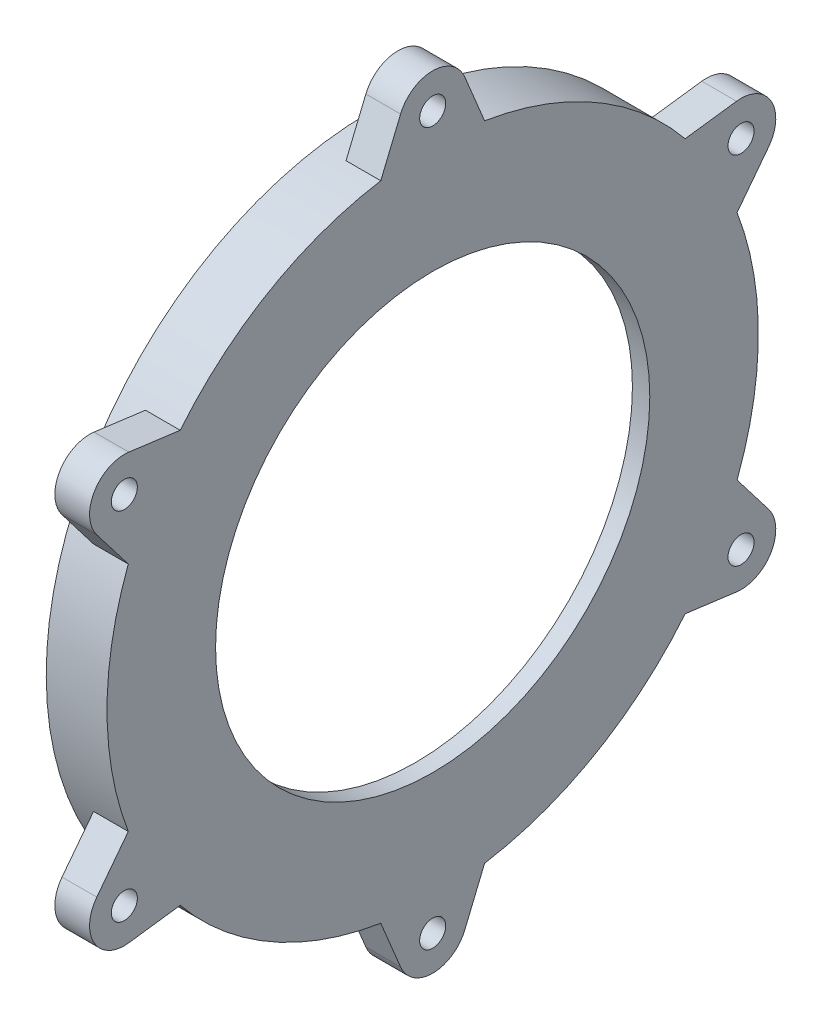
SolidWorks part; units mm, degrees
note: The reader was unsure of these and kept them because the rebuilt part matched: shared geometry of "TooCutSke<2>".
ref_plane "Plane1" through (0, 0, 0) normal (0, 0, 1) x (1, 0, 0)
ref_plane "Plane2" through (0, 0, 0) normal (0, 1, 0) x (1, 0, 0)
ref_plane "Plane3" through (0, 0, 0) normal (1, 0, 0) x (0, 0, -1)
sketch "HoldingSke" plane through (0, 0, 0) normal (0, 1, 0) x (1, 0, 0)
  line L0 (0, 0) -> (0.3746, -0.9272)
  line L1 (-15, 0) -> (100, 0) construction
  line L2 (0, 0) -> (-2.1039, 2.3779)
  line L3 (0, 0) -> (-11.863, 4.5341)
  line L4 (0, 0) -> (3.2351, 8.0072)
  line L5 (0, 0) -> (-23.7986, -8.8762)
  line L6 (0, 0) -> (-10.5278, -7.1032)
  line L7 (-2.1039, 2.3779) -> (3.3635, 27.1825)
  line L8 (-76.2, 3.3779) -> (-54.61, 3.3779)
  line L9 (-71.009, 38.7566) -> (-53.1078, 45.2721)
  line L10 (-76.2, 71.12) -> (104.1128, 71.12)
  line L11 (0, 0) -> (-5, 0)
  line L12 (-76.2, 101.6) -> (-76.162, 101.6)
  line L13 (24.9733, 27.94) -> (52.9518, 28.4284)
  line L14 (24.9733, 27.94) -> (24.9743, 27.94)
  line L15 (24.9733, 27.94) -> (100.4006, 29.5858)
  circle A0 centre (0, 0) radius 13
  circle A1 centre (0, 0) radius 12.7
  circle A2 centre (0, 0) radius 12.7
  dimension "MHD" = 25.4
  dimension "Hub_dia" = 25.4
  dimension "Diameter" = 26
  dimension "Num_teeth" = 68
  dimension "Pitch" = 1
  dimension "Overall_len" = 25.4
  dimension "Show_teeth" = 68
  dimension "Thickness" = 12.7
  dimension "OAL" = 25.4001
  dimension "T_dim" = 21.59
  dimension "Ap" = 20
  dimension "H" = 19.05
  dimension "Pitch_radius" = 180.3128
  dimension "Width" = 5
  dimension "Backlash" = 0.038
  dimension "Addendum_fac" = 1
  dimension "Dedendum_fac" = 1.25
  dimension "Clearance_fac" = 0.25
  dimension "Dedendum_add" = 0.001
  dimension "Module" = 1
sketch "BasProSke" plane through (0, 0, 0) normal (0, 1, 0) x (1, 0, 0)
  line L0 (-10, 0) -> (60, 0) construction
  line L1 (0, 33) -> (0, 35.2764)
  line L2 (0, 33) -> (5, 33)
  line L3 (5, 33) -> (5, 35.2764)
  line L4 (5, 35.2764) -> (0, 35.2764)
  dimension "Thickness" = 5
  dimension "Diameter" = 70.5528
  dimension "Inside_diameter" = 66
revolve "Base-Revolve" add sketch "BasProSke" angle 360 about L0
sketch "Эскиз1" plane through (0, 0, 0) normal (1, 0, 0) x (0, 0, -1)
  circle A0 centre (0, 0) radius 35.2764
  circle A1 centre (0, 0) radius 37.5
  circle A2 centre (0, 0) radius 35.2764 construction
  dimension "D1" = 75
extrude "Бобышка-Вытянуть1" add sketch "Эскиз1" along normal blind 5
sketch "Эскиз2" plane through (0, 0, 0) normal (1, 0, 0) x (0, 0, -1)
  circle A0 centre (0, 0) radius 33
curve "Спираль1" pitch 797.27 height 10 radius 33 left hand yes centre (0, 0, 0) axis (1, 0, 0) start towards (0, 0, 1)
sketch "TooCutSke" plane through (0, 0, 0) normal (1, 0, 0) x (0, 0, -1)
  line L3 (0.8803, 33.9886) -> (0.8803, 53.6633) construction
  line L4 (0, 0) -> (0, 59.563) construction
  line L5 (0, 0) -> (-3.1556, 68.2546) construction
  line L6 (-15.0631, 28.0889) -> (36.4744, 30.4716) construction
  circle A0 centre (0, 0) radius 34 construction
  circle A1 centre (0, 0) radius 35.251 construction
  circle A2 centre (0, 0) radius 28.7546 construction
  circle A3 centre (0, 0) radius 32.9746 construction
  arc A4 (1.2265, 32.9518) -> (0.3554, 35.2492) centre (-15.0631, 28.0889) ccw
  arc A5 (1.2265, 32.9518) -> (-1.2265, 32.9518) centre (0, 0) ccw
  arc A6 (0.3554, 35.2492) -> (-0.3554, 35.2492) centre (0, 0) ccw
  arc A7 (-0.3554, 35.2492) -> (-1.2265, 32.9518) centre (15.0631, 28.0889) ccw
  dimension "Pitch_dia" = 68
  dimension "Base_dia" = 57.5092
  dimension "Root_dia" = 70.502
  dimension "Overcut_dia" = 65.9492
  dimension "Flank_rad" = 17
  dimension "Half_ang" = 2.647
  dimension "Half_CT" = 0.8803
extrude "ToothCut" [suppressed] cut sketch "TooCutSke" along normal through all
sweep "Вырез-По траектории1" cut profiles "TooCutSke<2>" path "Спираль1" align with end faces yes
sketch "TooCutSke<2>" plane through (0, 0, 0) normal (1, 0, 0) x (0, 0, -1) same geometry as "TooCutSke"
fillet "Breaks" [suppressed] radius 0.1
fillet "RootFillets" [suppressed] radius 0.251
pattern_circular "TeethCuts" count 68 every 5.294 about axis through (-10, 0, 0) along (1, 0, 0) of "Вырез-По траектории1"
sketch "Эскиз3" plane through (5, 0, 0) normal (1, 0, 0) x (0, 0, -1)
  circle A0 centre (0, 0) radius 37.5
  circle A1 centre (0, 0) radius 37.5 construction
  circle A2 centre (0, 0) radius 25
  dimension "D1" = 50
extrude "Бобышка-Вытянуть2" add sketch "Эскиз3" along normal blind 2
sketch "Эскиз4" plane through (7, 0, 0) normal (1, 0, 0) x (0, 0, -1)
  line L0 (-3.6955, 42.5307) -> (-5.978, 37.0205)
  line L1 (0, 41) -> (0, 37.5) construction
  line L2 (3.6955, 42.5307) -> (5.978, 37.0205)
  circle A0 centre (0, 41) radius 1.5
  arc A1 (3.6955, 42.5307) -> (-3.6955, 42.5307) centre (0, 41) ccw
  circle A2 centre (0, 0) radius 37.5 construction
  arc A3 (-5.978, 37.0205) -> (5.978, 37.0205) centre (0, 0) cw
  dimension "D1" = 3
  dimension "D2" = 8
  dimension "D3" = 45
  dimension "D4" = 41
extrude "Бобышка-Вытянуть3" add sketch "Эскиз4" against normal blind 4
pattern_circular "Круговой массив1" count 6 over 360 about axis through (0, 0, 0) along (1, 0, 0) of "Бобышка-Вытянуть3"
equation "' \"Module@HoldingSke\" = 6.35"
equation "' \"Num_teeth@HoldingSke\" = 24"
equation "' \"Ap@HoldingSke\" =  14.5"
equation "' \"Ap@HoldingSke\" = 14.5"
equation "' \"Width@HoldingSke\" = 12"
equation "' \"Diameter@HoldingSke\" = 8 * 25.4"
equation "' \"Show_teeth@HoldingSke\" = 100"
equation "' \"Backlash@HoldingSke\" = 0.009 * 25.4"
equation "' \"Addendum_fac@HoldingSke\" = 1.0"
equation "' \"Dedendum_fac@HoldingSke\" = 1.25"
equation "' \"Dedendum_add@HoldingSke\" = 0.00005 * 25.4"
equation "' \"Clearance_fac@HoldingSke\" = 0.25"
equation "\"Pitch@HoldingSke\" = 1 / \"Module@HoldingSke\" "
equation "\"Overcut_dia@TooCutSke\" = (\"Num_teeth@HoldingSke\" - 2 * \"Addendum_fac@HoldingSke\") / \"Pitch@HoldingSke\" - 0.002 * 25.4"
equation "\"Pitch_dia@TooCutSke\" = \"Num_teeth@HoldingSke\" / \"Pitch@HoldingSke\""
equation "\"Base_dia@TooCutSke\" = \"Num_teeth@HoldingSke\" / \"Pitch@HoldingSke\" * cos((\"Ap@HoldingSke\"  * 3.14159265 / 180)) * 0.90"
equation "\"Root_dia@TooCutSke\" = \"Num_teeth@HoldingSke\"  / \"Pitch@HoldingSke\" + 2 *  \"Dedendum_fac@HoldingSke\"/ \"Pitch@HoldingSke\" + \"Dedendum_add@HoldingSke\" * 2"
equation "\"Half_ang@TooCutSke\" = 180 / \"Num_teeth@HoldingSke\""
equation "\"Half_CT@TooCutSke\" = \"Num_teeth@HoldingSke\" / \"Pitch@HoldingSke\" * sin((3.14159265 / 2 / \"Num_teeth@HoldingSke\")) / 2 + 10 * \"Backlash@HoldingSke\" / 4"
equation "\"Flank_rad@TooCutSke\" = \"Num_teeth@HoldingSke\" / \"Pitch@HoldingSke\" / 4"
equation "\"Radius@RootFillets\"= \"Clearance_fac@HoldingSke\" / \"Pitch@HoldingSke\" + \"Dedendum_add@HoldingSke\""
equation "\"Break_rad@Breaks\" = 0.02 / \"Pitch@HoldingSke\" * 5"
equation "\"Num_teeth@TeethCuts\" = int( \"Show_teeth@HoldingSke\" ) + 1"
equation "\"Num_teeth@TeethCuts\" = ((sgn( \"Num_teeth@TeethCuts\" - \"Num_teeth@HoldingSke\" )-1)*( \"Num_teeth@TeethCuts\" - \"Num_teeth@HoldingSke\" ))/-2+ \"Num_teeth@HoldingSke\""
equation "\"Num_teeth@TeethCuts\" = ((sgn( \"Num_teeth@TeethCuts\" - 2.0)+1)*( \"Num_teeth@TeethCuts\" - 2.0))/2 +2.0"
equation "\"Angle@TeethCuts\" = 360.0 / \"Num_teeth@HoldingSke\""
equation "\"Diameter@BasProSke\" = \"Num_teeth@HoldingSke\"  / \"Pitch@HoldingSke\" + 2 *  \"Dedendum_fac@HoldingSke\"/ \"Pitch@HoldingSke\" + \"Dedendum_add@HoldingSke\" * 2 + 0.002 * 25.4"
equation "\"Diameter@BasProSke\" = ((sgn( \"Diameter@BasProSke\"  - \"Diameter@HoldingSke\" )+1)*( \"Diameter@BasProSke\"  - \"Diameter@HoldingSke\" ))/2 + \"Diameter@HoldingSke\""
equation "\"Inside_diameter@BasProSke\" =  (\"Num_teeth@HoldingSke\" - 2 * \"Addendum_fac@HoldingSke\") / \"Pitch@HoldingSke\" "
equation "\"Thickness@BasProSke\"  = \"Width@HoldingSke\""
